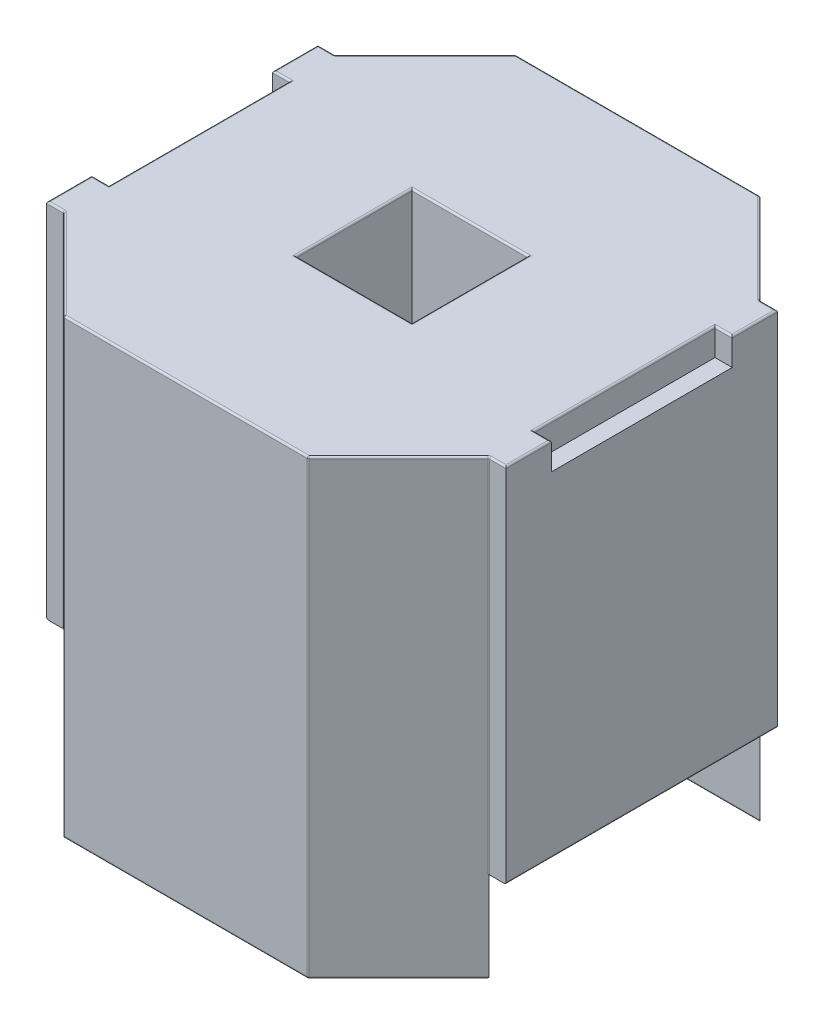
SolidWorks part; units mm, degrees
ref_plane "前视基准面" through (0, 0, 0) normal (0, 0, 1) x (1, 0, 0)
ref_plane "上视基准面" through (0, 0, 0) normal (0, 1, 0) x (1, 0, 0)
ref_plane "右视基准面" through (0, 0, 0) normal (1, 0, 0) x (0, 0, -1)
sketch "Sketch5" plane through (0, 0, 0) normal (0, 1, 0) x (1, 0, 0)
  line L0 (-0.675, 1.25) -> (-1.175, 0.75)
  line L1 (-0.675, 1.25) -> (0.675, 1.25)
  line L2 (-1.175, 0.75) -> (-1.175, -0.75)
  line L3 (-0.675, -1.25) -> (0.675, -1.25)
  line L4 (1.175, 0.75) -> (1.175, -0.75)
  line L7 (0, 1.25) -> (0, -1.25) construction
  line L8 (0.675, 1.25) -> (1.175, 0.75)
  line L9 (-1.175, 0) -> (1.175, 0) construction
  line L10 (0.675, -1.25) -> (1.175, -0.75)
  line L11 (-0.675, -1.25) -> (-1.175, -0.75)
  point P0 (0, 0)
  point P20 (0, 0)
  point P22 (0, -1.25)
  dimension "D1" = 2.35
  dimension "D2" = 2.5
  dimension "D3" = 0.5
  dimension "D4" = 0.5
extrude "Boss-Extrude1" add sketch "Sketch5" along normal blind 2.5
sketch "Sketch7" plane through (0, 2.5, 0) normal (0, 1, 0) x (1, 0, 0)
  line L1 (-0.32, 0.32) -> (0.32, 0.32)
  line L2 (-0.32, 0.32) -> (-0.32, -0.32)
  line L3 (-0.32, -0.32) -> (0.32, -0.32)
  line L4 (0.32, 0.32) -> (0.32, -0.32)
  line L5 (-0.32, 0.32) -> (0.32, -0.32) construction
  line L6 (-0.32, -0.32) -> (0.32, 0.32) construction
  point P0 (0, 0)
  dimension "D1" = 0.64
  dimension "D2" = 0.64
extrude "Cut-Extrude1" cut sketch "Sketch7" against normal through all
sketch "Sketch8" plane through (0, 2.5, 0) normal (0, 1, 0) x (1, 0, 0)
  line L0 (0, 1.25) -> (0, -1.25) construction
  line L1 (-1.27, -0.75) -> (-1.175, -0.75)
  line L2 (-1.27, -0.75) -> (-1.27, 0.75)
  line L3 (-1.27, 0.75) -> (-1.175, 0.75)
  line L4 (-1.175, -0.75) -> (-1.175, 0.75)
  line L5 (-1.27, -0.75) -> (-1.175, 0.75) construction
  line L6 (-1.27, 0.75) -> (-1.175, -0.75) construction
  line L7 (-0.675, -1.25) -> (0.675, -1.25) construction
  line L8 (0.675, 1.25) -> (-0.675, 1.25) construction
  line L9 (1.27, 0.75) -> (1.175, -0.75) construction
  line L10 (1.27, -0.75) -> (1.175, 0.75) construction
  line L11 (1.175, -0.75) -> (1.175, 0.75)
  line L12 (1.27, 0.75) -> (1.175, 0.75)
  line L13 (1.27, -0.75) -> (1.27, 0.75)
  line L14 (1.27, -0.75) -> (1.175, -0.75)
  point P0 (-1.2225, 0)
  point P17 (1.2225, 0)
  dimension "D1" = 2.54
extrude "Boss-Extrude2" add sketch "Sketch8" against normal up to surface (2.5 mm away) up to face at (0, 0, 0)
sketch "Sketch9" plane through (0, 2.5, 0) normal (0, 1, 0) x (1, 0, 0)
  line L0 (-1.27, 0) -> (1.27, 0) construction
  line L1 (-1.27, 0.75) -> (-1.27, -0.75) construction
  line L2 (1.27, -0.75) -> (1.27, 0.75) construction
  line L3 (0, 1.25) -> (0, -1.25) construction
  line L4 (-1.175, 0.5) -> (-1.27, 0.5)
  line L5 (-1.175, 0.5) -> (-1.175, -0.5)
  line L6 (-1.175, -0.5) -> (-1.27, -0.5)
  line L7 (-1.27, 0.5) -> (-1.27, -0.5)
  line L8 (-1.175, 0.5) -> (-1.27, -0.5) construction
  line L9 (-1.175, -0.5) -> (-1.27, 0.5) construction
  line L10 (0.675, 1.25) -> (-0.675, 1.25) construction
  line L11 (-0.675, -1.25) -> (0.675, -1.25) construction
  line L12 (1.175, -0.5) -> (1.27, 0.5) construction
  line L13 (1.175, 0.5) -> (1.27, -0.5) construction
  line L14 (1.27, 0.5) -> (1.27, -0.5)
  line L15 (1.175, -0.5) -> (1.27, -0.5)
  line L16 (1.175, 0.5) -> (1.175, -0.5)
  line L17 (1.175, 0.5) -> (1.27, 0.5)
  point P6 (-1.2225, 0)
  point P22 (1.2225, 0)
  dimension "D1" = 1
extrude "Cut-Extrude2" cut sketch "Sketch9" against normal blind 0.15
ref_plane "Plane3" through (10, 0, 0) normal (1, 0, 0) x (0, 0, -1)
sketch "Sketch12" plane through (1.27, 0, 0) normal (1, 0, 0) x (0, 0, -1)
  line L0 (0, 2.5) -> (0, 0) construction
  line L2 (0.5, 2.5) -> (-0.5, 2.5) construction
  line L7 (0.5, 2.5) -> (0.75, 2.5) construction
  line L8 (-0.75, 0.5) -> (0.75, 0.5)
  line L9 (-0.75, 0.5) -> (-0.75, 0)
  line L10 (-0.75, 0) -> (0.75, 0)
  line L11 (0.75, 0.5) -> (0.75, 0)
  line L12 (-0.75, 0.5) -> (0.75, 0) construction
  line L13 (-0.75, 0) -> (0.75, 0.5) construction
  line L14 (-0.75, 0) -> (0.75, 0) construction
  line L15 (0.75, 0) -> (0.75, 2.5) construction
  point P5 (0, 0.25)
  dimension "D1" = 2
extrude "Cut-Extrude3" cut sketch "Sketch12" against normal through all both and the other way through all
chamfer "Chamfer1" distance 0.4 angle 45 4 edges at (-0.32, 0.5, 0) (0, 0.5, 0.32) (0.32, 0.5, 0) (0, 0.5, -0.32)
fillet "Fillet1" radius 0.01 42 edges at (-1.2225, 2.5, -0.75) (-0.925, 2.5, -1) (0, 2.5, -1.25) (0.925, 2.5, -1) (1.2225, 2.5, -0.75) (1.27, 2.5, -0.625) (1.2225, 2.5, -0.5) (1.175, 2.5, 0) (1.2225, 2.5, 0.5) (1.27, 2.5, 0.625) (1.2225, 2.5, 0.75) (0.925, 2.5, 1) (0, 2.5, 1.25) (-0.925, 2.5, 1) (-1.2225, 2.5, 0.75) (-1.27, 2.5, 0.625) (-1.2225, 2.5, 0.5) (-1.175, 2.5, 0) (-1.2225, 2.5, -0.5) (-1.27, 2.5, -0.625) (-0.32, 2.5, 0) (0, 2.5, 0.32) (0.32, 2.5, 0) (0, 2.5, -0.32) (0.925, 0, -1) (-0.925, 0, -1) (0, 0, -0.75) (-0.925, 0, 1) (0.925, 0, 1) (0, 0, 0.75) (0.675, 1.25, -1.25) (-0.675, 1.25, -1.25) (0, 0, -1.25) (-0.675, 1.25, 1.25) (0.675, 1.25, 1.25) (0, 0, 1.25) (-1.27, 0.5, 0) (1.27, 0.5, 0) (-1.175, 1.5, -0.75) (-1.175, 1.5, 0.75) (1.175, 1.5, -0.75) (1.175, 1.5, 0.75)
